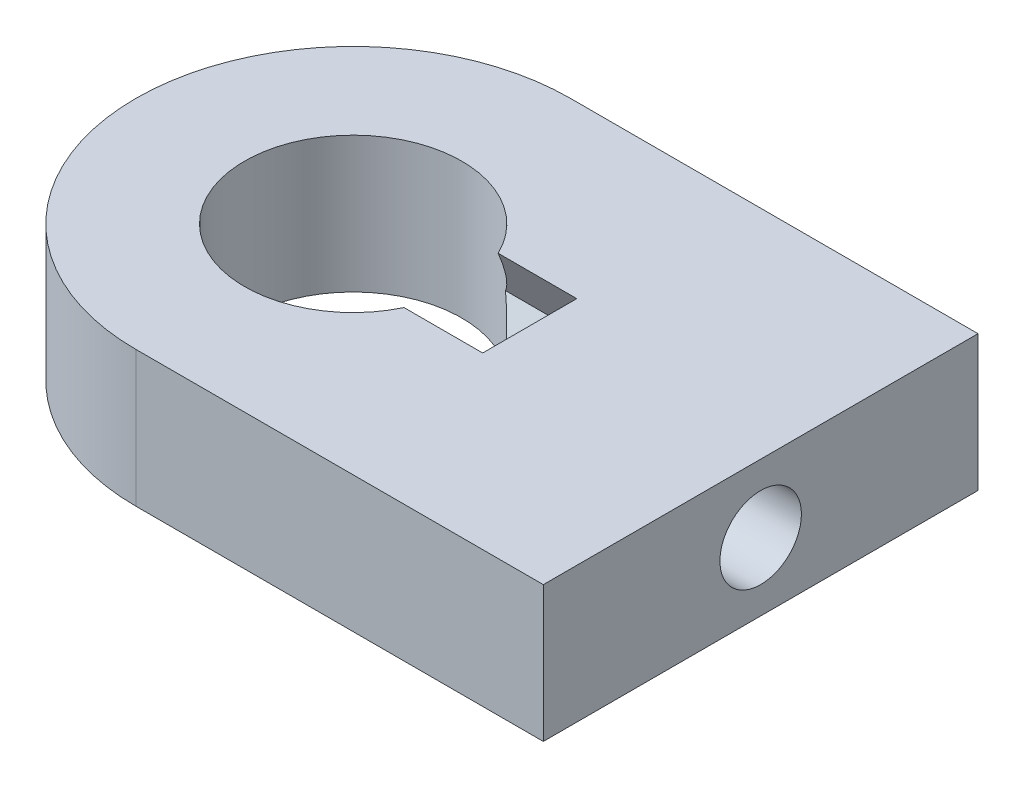
SolidWorks part; units mm, degrees
material "ABS"
ref_plane "Front Plane" through (0, 0, 0) normal (0, 0, 1) x (1, 0, 0)
ref_plane "Top Plane" through (0, 0, 0) normal (0, 1, 0) x (1, 0, 0)
ref_plane "Right Plane" through (0, 0, 0) normal (1, 0, 0) x (0, 0, -1)
sketch "Sketch1" plane through (0, 0, 0) normal (0, 1, 0) x (1, 0, 0)
  line L0 (0, 8) -> (15, 8)
  line L1 (15, 8) -> (15, -8)
  line L2 (15, -8) -> (0, -8)
  circle A0 centre (0, 0) radius 4
  arc A1 (0, -8) -> (0, 8) centre (0, 0) cw
  dimension "D1" = 8
  dimension "D2" = 8
  dimension "D3" = 15
extrude "Boss-Extrude1" add sketch "Sketch1" along normal blind 5
sketch "Sketch2" plane through (15, 0, 0) normal (1, 0, 0) x (0, 0, -1)
  line L0 (0, -3.0185) -> (0, 8.0813) construction
  line L1 (3.1754, 2.5) -> (1.5877, 5.25)
  line L2 (1.5877, 5.25) -> (-1.5877, 5.25)
  line L3 (-1.5877, 5.25) -> (-3.1754, 2.5)
  line L4 (-3.1754, 2.5) -> (-1.5877, -0.25)
  line L5 (-1.5877, -0.25) -> (1.5877, -0.25)
  line L6 (1.5877, -0.25) -> (3.1754, 2.5)
  line L7 (-8, 2.5) -> (8, 2.5) construction
  line L9 (-8, 5) -> (-8, 0) construction
  line L10 (8, 5) -> (8, 0) construction
  circle A0 centre (0, 2.5) radius 2.75 construction
  circle A1 centre (0, 2.5) radius 1.5
  dimension "D1" = 5.5
  dimension "D2" = 3
extrude "Cut-Extrude1" cut sketch "Sketch2" against normal up to next contours A1 region at (15, 2.5, 0)
sketch "Sketch3" plane through (0, 5, 0) normal (0, 1, 0) x (1, 0, 0)
  line L0 (6.5, 9.4882) -> (6.5, -10.0981) construction
  line L1 (0, -8) -> (15, -8) construction
  circle A0 centre (0, 0) radius 4 construction
  point P4 (6.5, -8)
  dimension "D1" = 6.5
extrude "Cut-Extrude2" cut sketch "Sketch2<4>" against normal up to next from vertex starting at point (6.5, 5, 8)
sketch "Sketch2<4>" plane through (15, 0, 0) normal (1, 0, 0) x (0, 0, -1) same geometry as "Sketch2"
equation "\"rod_diameter\"= 8"
equation "\"rod_hole_thickness\"= 4"
equation "\"rod_radius\"= \"rod_diameter\" / 2"
equation "\"platter_diameter\"= 320"
equation "\"platter_radius\"= \"platter_diameter\" / 2"
equation "\"extruder_mount_hole_spacing\"= 75"
equation "\"arm_rod_spacing\"= 40"
equation "\"top_frame_rod_spacing\"= \"arm_rod_spacing\" + 40"
equation "\"motor_level_rod_spacing\"= 15"
equation "\"linear_bearing_diameter\"= 15"
equation "\"z_rod_spacing\"= 75"
equation "\"platter_rod_spacing\"= 50"
equation "\"rod_nut_thickness\"= 6.5"
equation "\"rod_nut_inscribed_diameter\"= 13"
equation "\"z_height\"= 400"
equation "\"gear_pitch\"=2"
equation "\"r_gear_teeth\"= 450"
equation "\"theta_gear_teeth\"= 385"
equation "\"D1@Sketch1\"= \"rod_diameter\""
equation "\"D2@Sketch1\"=\"rod_radius\"+\"rod_hole_thickness\""
equation "\"D1@Sketch3\"=\"rod_radius\"+2.5"
